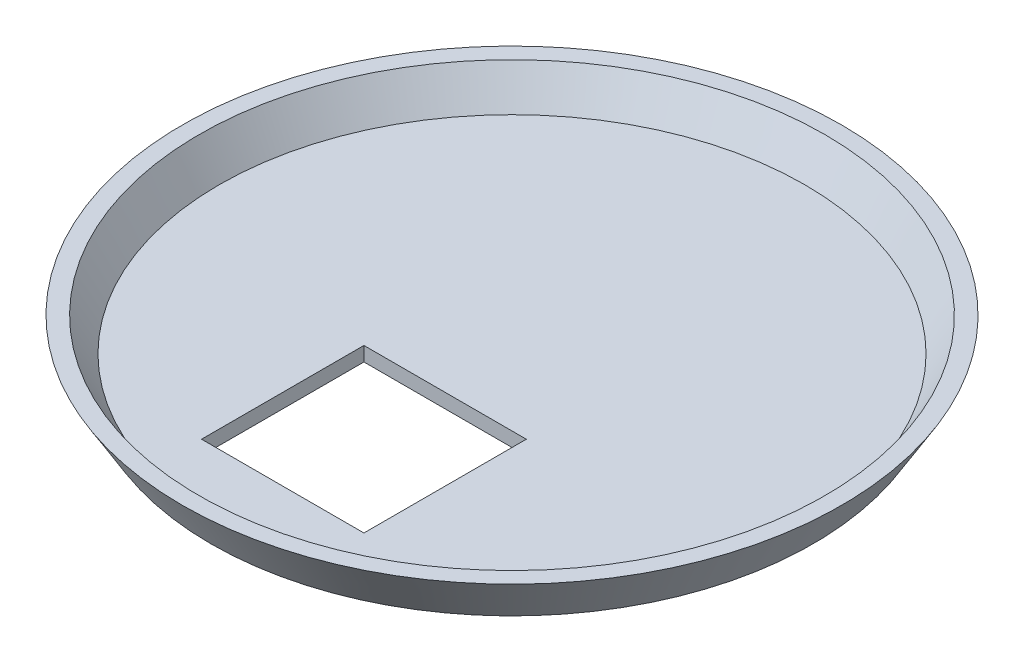
SolidWorks part; units mm, degrees
ref_plane "Front Plane" through (0, 0, 0) normal (0, 0, 1) x (1, 0, 0)
ref_plane "Top Plane" through (0, 0, 0) normal (0, 1, 0) x (1, 0, 0)
ref_plane "Right Plane" through (0, 0, 0) normal (1, 0, 0) x (0, 0, -1)
sketch "Sketch1" plane through (0, 0, 0) normal (0, 0, 1) x (1, 0, 0)
  line L0 (0, 0) -> (63, 0)
  line L1 (63, 0) -> (69, 10)
  line L6 (0, 3) -> (61.3014, 3)
  line L7 (61.3014, 3) -> (65.5014, 10)
  line L8 (69, 10) -> (65.5014, 10)
  line L9 (0, 0) -> (0, 3)
  line L10 (61.3014, 3) -> (66.4275, 11.5435) construction
  dimension "D1" = 69
  dimension "D2" = 63
  dimension "D3" = 10
  dimension "D4" = 3
revolve "Revolve1" add sketch "Sketch1" angle 360 about L9
sketch "Sketch2" plane through (0, 0, 0) normal (0, -1, 0) x (1, 0, 0)
  line L1 (-17, 48) -> (17, 48)
  line L2 (-17, 48) -> (-17, 14)
  line L3 (-17, 14) -> (17, 14)
  line L4 (17, 48) -> (17, 14)
  dimension "D1" = 34
  dimension "D2" = 34
  dimension "D3" = 17
  dimension "D4" = 14
extrude "Cut-Extrude1" cut sketch "Sketch2" against normal through all
